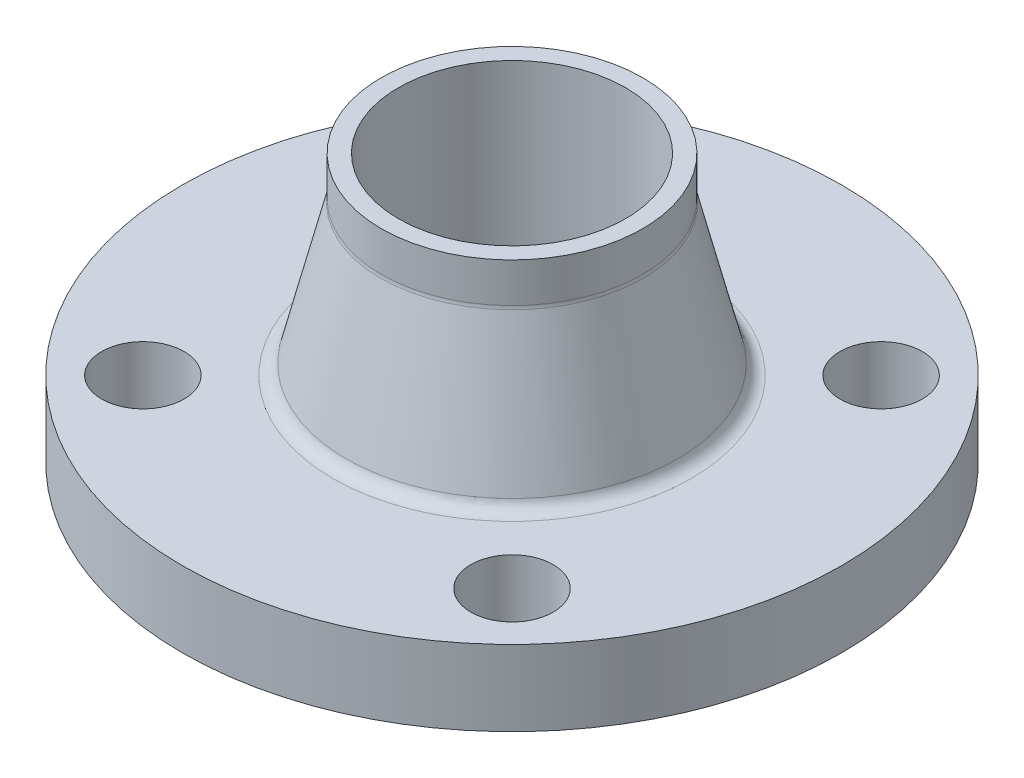
SolidWorks part; units mm, degrees
ref_plane "Plane1" through (0, 0, 0) normal (0, 0, 1) x (1, 0, 0)
ref_plane "Plane2" through (0, 0, 0) normal (0, 1, 0) x (1, 0, 0)
ref_plane "Plane3" through (0, 0, 0) normal (1, 0, 0) x (0, 0, -1)
sketch "Sketch3" plane through (0, 0, 0) normal (0, 0, 1) x (1, 0, 0)
  line L0 (0, 0) -> (0, 68.58) construction
  line L1 (26.2509, 61.9125) -> (26.2509, -1.5875)
  line L2 (26.2509, -1.5875) -> (46.0375, -1.5875)
  line L3 (46.0375, -1.5875) -> (46.0375, 0)
  line L4 (46.0375, 0) -> (76.2, 0)
  line L5 (76.2, 0) -> (76.2, 17.4625)
  line L6 (76.2, 17.4625) -> (41.3771, 17.4625)
  line L7 (38.2956, 19.8727) -> (30.3195, 52.0108)
  line L8 (30.226, 52.7756) -> (30.226, 61.9125)
  line L10 (30.226, 61.9125) -> (26.2509, 61.9125)
  line L11 (41.3771, 17.4625) -> (38.8937, 17.4625) construction
  line L12 (37.7455, 22.0893) -> (38.8937, 17.4625) construction
  arc A0 (41.3771, 17.4625) -> (38.2956, 19.8727) centre (41.3771, 20.6375) cw
  arc A1 (30.3195, 52.0108) -> (30.226, 52.7756) centre (33.401, 52.7756) cw
  point P18 (30.226, 52.3875)
  dimension "D3" = 9.525
revolve "Base-Revolve" add sketch "Sketch3" angle 360 about L0
sketch "Sketch4" plane through (0, 17.4625, 0) normal (0, 1, 0) x (-1, 0, 0)
  line L0 (-87.63, 0) -> (93.98, 0) construction
  line L1 (0, -100.33) -> (0, 93.98) construction
  line L2 (-42.6562, 42.6562) -> (0, 0) construction
  line L3 (0, 0) -> (62.23, 62.23) construction
  circle A0 centre (-42.6562, 42.6562) radius 9.525
  dimension "Bolt Hole Dia" = 19.05
  dimension "Bolt Hole Angle" = 45
  dimension "Bolt Circle Dia" = 120.65
extrude "1st Bolt Hole" cut sketch "Sketch4" against normal through all
ref_axis "Axis1" through (0, 17.4625, 0) along (0, -1, 0)
pattern_circular "Bolt Hole Pattern" count 4 over 360 about axis through (0, 17.4625, 0) along (0, -1, 0) of "1st Bolt Hole"
ref_plane "CP Offset Plane" through (0, 63.5, 0) normal (0, 1, 0) x (-1, 0, 0)
sketch "CP Sketch Point" plane through (0, 63.5, 0) normal (0, 1, 0) x (-1, 0, 0)
  point P0 (0, 0)
other "CPoint1" parameters "Diameter"=50.8, "StubLength"=0
ref_axis "Axis2" through (0, 73.5, 0) along (0, -1, 0)
ref_axis "Mate Axis" through (42.6562, 0, 42.6562) along (0, 1, 0)
ref_plane "Mate Plane" through (0, 17.4625, 0) normal (0, 1, 0) x (-1, 0, 0)
equation "\"D3@Sketch3\"=\"Q@Sketch3\"/2"
